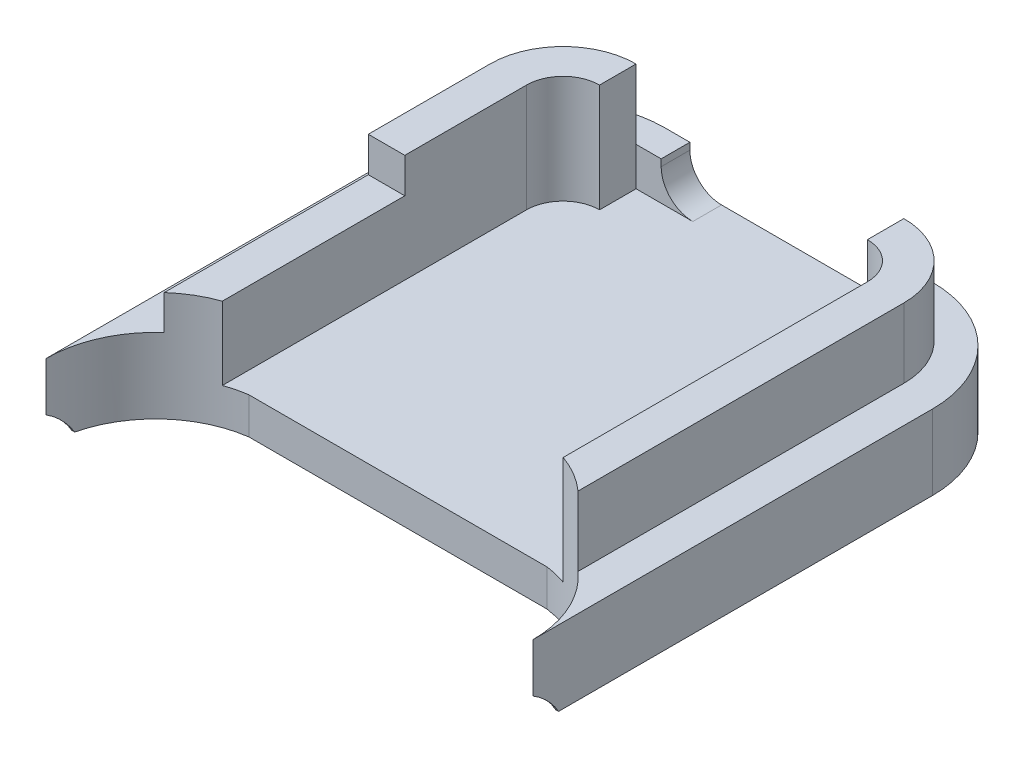
SolidWorks part; units mm, degrees
ref_plane "Front Plane" through (0, 0, 0) normal (0, 0, 1) x (1, 0, 0)
ref_plane "Top Plane" through (0, 0, 0) normal (0, 1, 0) x (1, 0, 0)
ref_plane "Right Plane" through (0, 0, 0) normal (1, 0, 0) x (0, 0, -1)
sketch "Sketch1" plane through (0, 0, 0) normal (0, 1, 0) x (1, 0, 0)
  line L0 (3, 25.18) -> (14, 25.18)
  line L1 (3, 0) -> (14, 0)
  line L2 (0, 3) -> (0, 21)
  line L3 (3, 24) -> (14, 24)
  line L4 (17, 3) -> (17, 21)
  line L5 (18.5, 2.68) -> (18.5, 20.68)
  line L6 (3, -1.5) -> (14, -1.5)
  line L7 (-1.5, 3) -> (-1.5, 21)
  arc A0 (17, 21) -> (14, 24) centre (14, 21) ccw
  arc A1 (14, 0) -> (17, 3) centre (14, 3) ccw
  arc A2 (0, 3) -> (3, 0) centre (3, 3) ccw
  arc A3 (0, 21) -> (3, 24) centre (3, 21) cw
  arc A4 (18.5, 20.68) -> (14, 25.18) centre (14, 20.68) ccw
  arc A5 (14, -1.5) -> (18.5, 2.68) centre (14.0114, 3) ccw
  arc A6 (-1.5, 3) -> (3, -1.5) centre (3, 3) ccw
  arc A7 (-1.5, 21) -> (3, 25.18) centre (2.9886, 20.68) cw
  point P7 (17, 24)
  point P10 (17, 0)
  point P13 (0, 0)
  point P16 (0, 24)
  dimension "D3" = 3
  dimension "D1" = 17
  dimension "D2" = 24
  dimension "D5" = 1.5
  dimension "D4" = 1.18
  dimension "D6" = 1.5
ref_plane "Plane3" through (0, 3.23, 0) normal (0, 1, 0) x (1, 0, 0)
sketch "Sketch9" plane through (0, 3.23, 0) normal (0, 1, 0) x (1, 0, 0)
  line L0 (3, 25.18) -> (14, 25.18)
  line L2 (0, 3) -> (0, 21)
  line L3 (3, 24) -> (14, 24)
  line L4 (17, 3) -> (17, 21)
  line L5 (18.5, 3) -> (18.5, 20.68)
  line L7 (-1.5, 3) -> (-1.5, 21)
  line L17 (-1.5, 3) -> (0, 3)
  line L18 (17, 3) -> (18.5, 3)
  arc A0 (17, 21) -> (14, 24) centre (14, 21) ccw
  arc A3 (0, 21) -> (3, 24) centre (3, 21) cw
  arc A4 (18.5, 20.68) -> (14, 25.18) centre (14, 20.68) ccw
  arc A7 (-1.5, 21) -> (3, 25.18) centre (2.9886, 20.68) cw
  dimension "D1" = 3
  dimension "D2" = 1.18
  dimension "D3" = 1.5
  dimension "D7" = 24
extrude "Boss-Extrude6" add sketch "Sketch9" against normal blind 2.5
ref_plane "Plane1" through (0, 0, -25.18) normal (0, 0, -1) x (-1, 0, 0)
sketch "Sketch7" plane through (0, 0, -25.18) normal (0, 0, -1) x (-1, 0, 0)
  line L0 (-12.97, 3.23) -> (-4.03, 3.23)
  line L2 (-11.67, 1.65) -> (-5.33, 1.65)
  line L3 (-8.5, 3.23) -> (-8.5, -0.03) construction
  line L4 (-12.97, 3.23) -> (-12.97, 2.95)
  line L5 (-4.03, 3.23) -> (-4.03, 2.95)
  line L8 (-14, 3.23) -> (-3, 3.23) construction
  arc A0 (-11.67, 1.65) -> (-12.97, 2.95) centre (-11.67, 2.95) cw
  arc A1 (-5.33, 1.65) -> (-4.03, 2.95) centre (-5.33, 2.95) ccw
  point P4 (-8.5, 3.23)
  point P8 (-8.5, 1.65)
  dimension "D6" = 1.3
  dimension "D1" = 1.58
  dimension "D2" = 8.94
  dimension "D4" = 6.34
  dimension "D5" = 0
extrude "Cut-Extrude1" cut sketch "Sketch7" against normal blind 1.5 and the other way through all
ref_plane "Plane2" through (0, 2.86, 0) normal (0, 1, 0) x (1, 0, 0)
sketch "Sketch12" plane through (0, 0, 0) normal (1, 0, 0) x (0, 0, -1)
  line L2 (6.7873, 1.65) -> (1.6444, 1.65)
  line L33 (1.6444, 1.65) -> (1.6444, 0.15)
  line L34 (25.18, 0.15) -> (8.72, 0.15)
  line L43 (6.7873, 1.65) -> (25.18, 1.65)
  line L44 (25.18, -1.375) -> (25.18, 1.375) construction
  line L45 (25.18, 1.65) -> (25.18, 0.15)
  line L47 (1.6444, 0.15) -> (8.72, 0.15)
  dimension "D5" = 1.5
extrude "Boss-Extrude7" add sketch "Sketch12" along normal through all and the other way through all
sketch "Sketch14" plane through (0, 2.86, 0) normal (0, 1, 0) x (1, 0, 0)
  line L0 (3.0132, 26.68) -> (14.0114, 26.68)
  line L1 (20, 2.6304) -> (20, 20.68)
  line L4 (3, -7.38) -> (14, -7.38)
  line L6 (3, -8.88) -> (13.9982, -8.88)
  line L7 (-3, 3) -> (-3, 21.0496)
  line L8 (3.9557, -7.38) -> (12.9756, -7.38) construction
  line L9 (8.5, -1.5) -> (8.5, -9.0262) construction
  line L14 (-3, -2.88) -> (-3, -8.88)
  line L15 (-3, -8.88) -> (3, -8.88)
  line L16 (13.9982, -8.88) -> (20, -8.88)
  line L17 (20, -8.88) -> (20, -3.2496)
  line L18 (3, -1.5) -> (14, -1.5) construction
  line L19 (-3, 3) -> (-3, -2.88)
  line L20 (-1.5, 3) -> (-1.5, -2.88)
  line L22 (20, 2.6304) -> (20, -3.2496)
  line L23 (-3, 21.0496) -> (-3, 26.68)
  line L24 (-3, 26.68) -> (3.0132, 26.68)
  line L25 (14.0114, 26.68) -> (20, 26.68)
  line L26 (20, 26.68) -> (20, 20.68)
  line L27 (18.5, 3) -> (18.5, -2.88)
  line L28 (18.5, 3) -> (18.5, 20.68)
  line L29 (-1.5, 3) -> (-1.5, 21) construction
  line L30 (-1.5, 20.6914) -> (-1.5, 3)
  line L31 (14, 25.18) -> (3, 25.18)
  circle A0 centre (4.75, 1.52) radius 0.75
  circle A1 centre (7.25, 1.52) radius 0.75
  circle A2 centre (9.75, 1.52) radius 0.75
  circle A3 centre (12.25, 1.52) radius 0.75
  arc A6 (-1.5, -2.88) -> (3, -7.38) centre (3, -2.88) ccw
  arc A8 (2.9868, 26.68) -> (3.0132, 26.68) centre (3, 20.68) cw
  arc A10 (13.9982, -8.88) -> (14.0245, -8.88) centre (14.0114, -2.88) ccw
  arc A14 (18.5, -2.88) -> (14, -7.38) centre (14, -2.88) cw
  arc A16 (18.5, 20.68) -> (14, 25.18) centre (14, 20.68) ccw
  arc A17 (18.5, 20.68) -> (14, 25.18) centre (14, 20.68) ccw construction
  arc A18 (3, 25.18) -> (-1.5, 20.6914) centre (3, 20.68) ccw
  point P15 (0.4549, -0.0862)
  point P19 (17.4549, 23.9138)
  point P22 (0.4549, 23.9138)
  dimension "D1" = 1.5
  dimension "D7" = 4.5
  dimension "D2" = 17
  dimension "D3" = 4.5
  dimension "D4" = 1.52
  dimension "D5" = 4.75
  dimension "D6" = 5.88
extrude "Cut-Extrude2" cut sketch "Sketch14" against normal through all both and the other way through all contours L26 L25 L0 L24 L23 L7 L19 L14 L15 L6 L16 L17 L22 L1 L31 L4 A6 L20 | A0 | A1 | A2 | A3 region at (8.5123, 2.86, -26.2565) region at (4.75, 2.86, -1.52) region at (7.25, 2.86, -1.52) region at (9.75, 2.86, -1.52) region at (12.25, 2.86, -1.52)
ref_plane "Plane4" through (0, -6.85, 0) normal (0, -1, 0) x (-1, 0, 0)
ref_plane "Plane5" through (0, 1.65, 0) normal (0, 1, 0) x (1, 0, 0)
sketch "Sketch19" plane through (0, 1.65, 0) normal (0, 1, 0) x (1, 0, 0)
  line L0 (17, 21) -> (17, 16)
  line L1 (17, 3) -> (17, 21) construction
  line L2 (0, 21) -> (0, 16)
  line L4 (1.5, 21) -> (1.5, 16)
  line L5 (15.5, 21) -> (15.5, 16)
  line L6 (3, 24) -> (3, 22.5)
  line L7 (14, 24) -> (14, 22.5)
  line L10 (1.5, 3) -> (0, 3)
  line L12 (15.5, 7) -> (15.5, 3)
  line L13 (15.5, 3) -> (17, 3)
  line L14 (17, 7) -> (17, 3)
  line L15 (0, 3) -> (0, 7)
  line L16 (1.5, 7) -> (1.5, 3)
  line L17 (1.5, 16) -> (0, 16)
  line L18 (1.5, 7) -> (0, 7)
  line L19 (15.5, 16) -> (15.5, 7)
  line L20 (1.5, 21) -> (1.5, 13) construction
  line L21 (0, 21) -> (0, 13) construction
  line L22 (17, 7) -> (17, 16)
  arc A0 (3, 24) -> (0, 21) centre (3, 21) ccw
  arc A1 (3, 24) -> (0, 21) centre (3, 21) ccw construction
  arc A2 (17, 21) -> (14, 24) centre (14, 21) ccw
  arc A3 (17, 21) -> (14, 24) centre (14, 21) ccw construction
  arc A4 (3, 22.5) -> (1.5, 21) centre (3, 21) ccw
  arc A5 (15.5, 21) -> (14, 22.5) centre (14, 21) ccw
  dimension "D2" = 1.5
  dimension "D3" = 1.5
extrude "Boss-Extrude9" add sketch "Sketch19" along normal blind 4.44
ref_plane "Plane6" through (0, 0, -16) normal (0, 0, 1) x (1, 0, 0)
sketch "Sketch21" plane through (0, 0, -16) normal (0, 0, 1) x (1, 0, 0)
  line L0 (1.5, 6.09) -> (1.5, 1.65) construction
  line L1 (0, 1.65) -> (1.5, 1.65)
  line L2 (0, 1.65) -> (0, 4.65)
  line L3 (0, 4.65) -> (1.5, 4.65)
  line L4 (1.5, 1.65) -> (1.5, 4.65)
  dimension "D1" = 3
extrude "Boss-Extrude11" add sketch "Sketch21" along normal blind 10
sketch "Sketch17" plane through (0, -6.85, 0) normal (0, -1, 0) x (-1, 0, 0)
  line L1 (-18.5, 2.68) -> (-18.5, 20.68) construction
  line L2 (-8.5, 8.72) -> (-8.5, 5.1845) construction
  line L7 (-14.6206, 8.72) -> (-2.3794, 8.72)
  line L8 (1.5, 4.263) -> (1.5, -1.5)
  line L9 (1.5, -1.5) -> (-18.5, -1.5)
  line L10 (-18.5, -1.5) -> (-18.5, 4.263)
  arc A0 (-14.6206, 8.72) -> (-18.5, 4.263) centre (-14, 4.263) ccw
  arc A1 (-2.3794, 8.72) -> (1.5, 4.263) centre (-3, 4.263) cw
  dimension "D1" = 4.5
  dimension "D2" = 4.5
extrude "Cut-Extrude3" cut sketch "Sketch17" against normal through all and the other way through all
sketch "Sketch20" plane through (0, 0, 0) normal (1, 0, 0) x (0, 0, -1)
  line L2 (-1.38, 1.65) -> (0.12, 1.65)
  line L6 (0.12, 1.65) -> (2.72, 1.65)
  line L18 (-4.38, -1.35) -> (-4.38, -6.35)
  line L19 (5.72, -1.35) -> (5.72, -6.35)
  line L22 (-4.38, -7.8887) -> (5.72, -7.8887)
  line L26 (-4.38, -6.35) -> (-4.38, -7.8887)
  line L27 (5.72, -6.35) -> (5.72, -7.8887)
  arc A0 (-1.38, 1.65) -> (-4.38, -1.35) centre (-1.38, -1.35) ccw
  arc A1 (2.72, 1.65) -> (5.72, -1.35) centre (2.72, -1.35) cw
  dimension "D5" = 5
  dimension "D6" = 5
extrude "Cut-Extrude4" cut sketch "Sketch20" against normal through all both and the other way through all
